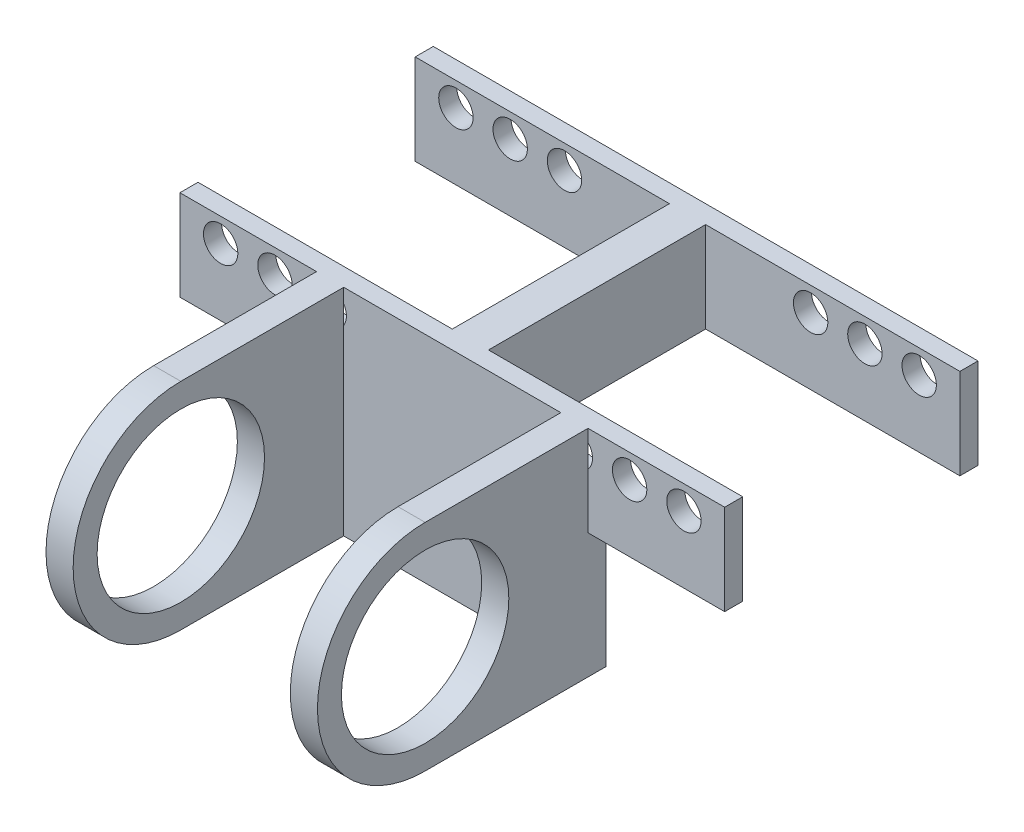
SolidWorks part; units mm, degrees
ref_plane "Front Plane" through (0, 0, 0) normal (0, 0, 1) x (1, 0, 0)
ref_plane "Top Plane" through (0, 0, 0) normal (0, 1, 0) x (1, 0, 0)
ref_plane "Right Plane" through (0, 0, 0) normal (1, 0, 0) x (0, 0, -1)
sketch "Sketch1" plane through (-91.9889, -76.5955, 0) normal (0, 0, 1) x (0, 1, 0)
  line L4 (45.2151, -102.4889) -> (55.2151, -102.4889)
  line L5 (45.2151, -102.4889) -> (45.2151, -42.2898)
  line L6 (45.2151, -42.2898) -> (55.2151, -42.2898)
  line L7 (55.2151, -102.4889) -> (55.2151, -42.2898)
  line L8 (45.2151, -72.3894) -> (55.2151, -72.3894) construction
  line L9 (50.2151, -42.2898) -> (50.2151, -102.4889) construction
  circle A3 centre (52.5955, -97.9889) radius 1.9
  circle A4 centre (52.5955, -91.9889) radius 1.9
  circle A5 centre (52.5955, -85.9889) radius 1.9
  circle A6 centre (52.5955, -58.7898) radius 1.9
  circle A7 centre (52.5955, -52.7898) radius 1.9
  circle A8 centre (52.5955, -46.7898) radius 1.9
  point P0 (52.5955, -85.9889)
  point P15 (0, 0)
  point P17 (0, 0)
  point P18 (0, 0)
  dimension "D1" = 3.8
  dimension "D2" = 10
extrude "Boss-Extrude1" add sketch "Sketch1" against normal blind 26 and the other way blind 2
sketch "Sketch2" plane through (0, -31.3804, 0) normal (0, -1, 0) x (1, 0, 0)
  line L0 (-49.6991, 2) -> (-49.6991, -26) construction
  line L1 (-49.6991, 0) -> (-21.5995, 0)
  line L2 (-49.6991, 0) -> (-49.6991, -24)
  line L3 (-49.6991, -24) -> (-21.5995, -24)
  line L4 (-21.5995, 0) -> (-21.5995, -24)
  line L5 (-19.5995, 2) -> (-19.5995, -26) construction
  line L6 (-49.6991, 2) -> (10.5, 2) construction
  line L7 (-49.6991, -26) -> (10.5, -26) construction
  line L8 (-17.5995, 0) -> (-17.5995, -24)
  line L9 (10.5, -24) -> (-17.5995, -24)
  line L10 (10.5, 0) -> (10.5, -24)
  line L11 (10.5, 0) -> (-17.5995, 0)
  point P12 (-21.5995, -12)
  point P13 (-19.5995, -12)
  dimension "D1" = 24
  dimension "D2" = 2
extrude "Cut-Extrude1" cut sketch "Sketch2" against normal blind 26
sketch "Sketch6" plane through (-21.5995, -143.1553, -4.4692) normal (-1, 0, 0) x (0, 0, -1)
  line L0 (-24.4692, -97.9749) -> (-4.4692, -97.9749)
  line L1 (-24.4692, -121.7749) -> (-6.4692, -121.7749)
  line L2 (-4.4692, -97.9749) -> (-4.4692, -111.7749)
  line L5 (-4.4692, -111.7749) -> (-6.4692, -111.7749)
  line L6 (-6.4692, -111.7749) -> (-6.4692, -121.7749)
  circle A0 centre (-24.4692, -109.8749) radius 9.25
  arc A1 (-24.4692, -97.9749) -> (-24.4692, -121.7749) centre (-24.4692, -109.8749) ccw
  dimension "D1" = 18.5
  dimension "D2" = 23.8
  dimension "D3" = 20
extrude "Boss-Extrude3" add sketch "Sketch6" along normal blind 13 and the other way blind 17
sketch "Sketch7" plane through (0, -45.1804, 0) normal (0, -1, 0) x (1, 0, 0)
  line L0 (-4.5995, 31.9) -> (-34.5995, 31.9) construction
  line L1 (-31.5995, 31.9) -> (-7.5995, 31.9)
  line L2 (-31.5995, 31.9) -> (-31.5995, 2)
  line L3 (-31.5995, 2) -> (-7.5995, 2)
  line L4 (-7.5995, 31.9) -> (-7.5995, 2)
  line L6 (-19.5995, 0) -> (-19.5995, 31.9) construction
  line L7 (-19.5995, 31.9) -> (-19.5995, 0) construction
  line L8 (-49.6991, 2) -> (-34.5995, 2) construction
  dimension "D1" = 24
extrude "Cut-Extrude3" cut sketch "Sketch7" against normal through all
